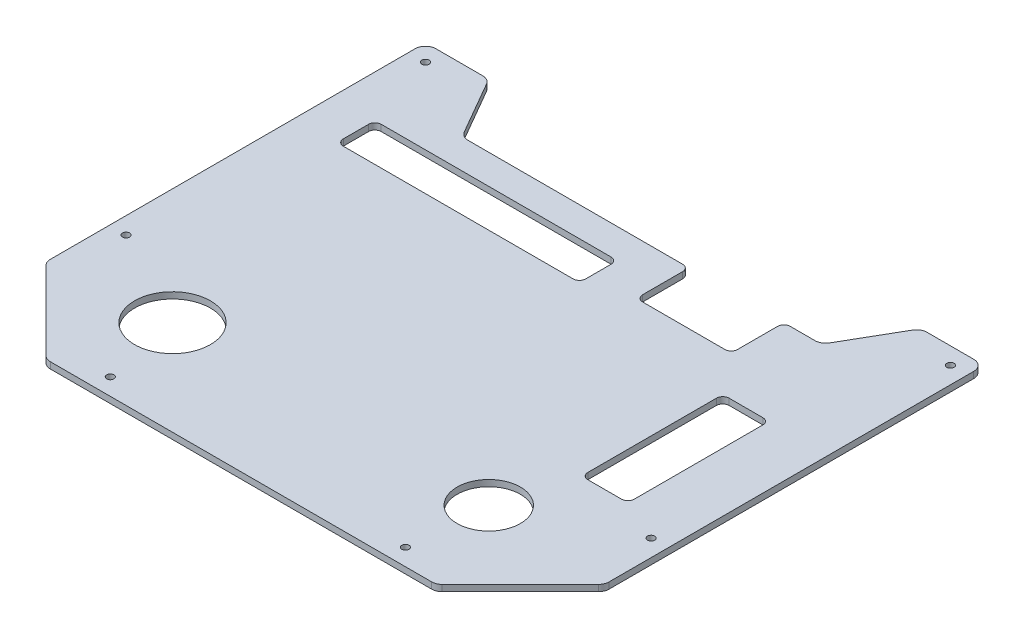
SolidWorks part; units mm, degrees
material "Acier non allié"
ref_plane "Front" through (0, 0, 0) normal (0, 0, 1) x (1, 0, 0)
ref_plane "Top" through (0, 0, 0) normal (0, 1, 0) x (1, 0, 0)
ref_plane "Right" through (0, 0, 0) normal (1, 0, 0) x (0, 0, -1)
sketch "Esquisse1" plane through (0, 0, 0) normal (0, 1, 0) x (1, 0, 0)
  line L0 (0, 0) -> (0, 1919.0564) construction
  line L1 (-92.5, 0) -> (92.5, 0)
  line L2 (92.5, 0) -> (132.5, 40)
  line L3 (132.5, 40) -> (132.5, 220)
  line L4 (132.5, 220) -> (102.5, 220)
  line L5 (102.5, 220) -> (85.1795, 190)
  line L6 (85.1795, 190) -> (-85.1795, 190)
  line L7 (-102.5, 220) -> (-85.1795, 190)
  line L8 (-132.5, 220) -> (-102.5, 220)
  line L9 (-132.5, 40) -> (-132.5, 220)
  line L10 (-92.5, 0) -> (-132.5, 40)
  point P12 (0, 190)
  dimension "D1" = 132.5
  dimension "D2" = 220
  dimension "D3" = 30
  dimension "D4" = 30
  dimension "D5" = 40
  dimension "D6" = 40
  dimension "D7" = 60
extrude "Boss.-Extru.1" add sketch "Esquisse1" along normal blind 3
fillet "Congé1" radius 5 10 edges at (132.5, 1.5, -220) (102.5, 1.5, -220) (85.1795, 1.5, -190) (-85.1795, 1.5, -190) (-102.5, 1.5, -220) (-132.5, 1.5, -220) (-132.5, 1.5, -40) (-92.5, 1.5, 0) (92.5, 1.5, 0) (132.5, 1.5, -40)
sketch "Esquisse2" plane through (0, 0, 0) normal (0, -1, 0) x (1, 0, 0)
  line L0 (0, 0) -> (0, -330.9968) construction
  line L1 (-90.4289, 0) -> (90.4289, 0) construction
  line L2 (-105.3868, -220) -> (-127.5, -220) construction
  line L3 (-132.5, -215) -> (-132.5, -42.0711) construction
  circle A0 centre (-70, -8) radius 1
  circle A1 centre (-124.5, -70) radius 1
  circle A2 centre (-124.5, -212) radius 1
  circle A3 centre (124.5, -212) radius 1
  circle A4 centre (124.5, -70) radius 1
  circle A5 centre (70, -8) radius 1
  dimension "D3" = 2
  dimension "D6" = 2
  dimension "D9" = 2
  dimension "D1" = 70
  dimension "D2" = 8
  dimension "D4" = 124.5
  dimension "D5" = 70
  dimension "D7" = 8
  dimension "D8" = 8
extrude "Enlèv. mat.-Extru.1" cut sketch "Esquisse2" against normal through all
hole_wizard "Dégagement M31" positions "Esquisse3" profile "Esquisse4" hole size "M3" standard "ISO" end condition through all
sketch "Esquisse3" plane through (0, 0, 0) normal (0, -1, 0) x (-1, 0, 0)
  point P0 (-70, 8)
  point P3 (-124.5, 70)
  point P6 (-124.5, 212)
  point P9 (124.5, 212)
  point P12 (124.5, 70)
  point P15 (70, 8)
sketch "Esquisse4" plane through (70, 0, -8) normal (1, 0, 0) x (0, 0, -1)
  line L0 (0, 0) -> (0, 3)
  line L1 (0, 3) -> (1.7, 3)
  line L2 (1.7, 3) -> (1.7, 0)
  line L5 (1.7, 0) -> (0, 0)
  line L11 (0, -6.35) -> (0, 107.95) construction
  dimension "Diamètre du perçage jusqu'au prochain" = 3.4
  dimension "Profondeur du perçage jusqu'au prochain" = 3
sketch "Esquisse5" plane through (0, 0, 0) normal (0, -1, 0) x (1, 0, 0)
  line L6 (82.2927, -190) -> (-82.2927, -190) construction
  line L7 (22.5, -190) -> (67.5, -190)
  line L20 (22.5, -190) -> (22.5, -165)
  line L21 (22.5, -165) -> (67.5, -165)
  line L22 (67.5, -190) -> (67.5, -165)
  line L23 (132.5, -42.0711) -> (132.5, -215) construction
  line L24 (-105.3868, -220) -> (-127.5, -220) construction
  line L25 (-112.5, -176) -> (2.5, -176)
  line L26 (-112.5, -176) -> (-112.5, -158)
  line L27 (-112.5, -158) -> (2.5, -158)
  line L28 (2.5, -176) -> (2.5, -158)
  line L29 (-132.5, -215) -> (-132.5, -42.0711) construction
  line L30 (127.5, -220) -> (105.3868, -220) construction
  line L31 (82.5, -146) -> (104.5, -146)
  line L32 (82.5, -146) -> (82.5, -79)
  line L33 (82.5, -79) -> (104.5, -79)
  line L34 (104.5, -146) -> (104.5, -79)
  line L35 (-90.4289, 0) -> (90.4289, 0) construction
  circle A0 centre (-77.5, -45) radius 18
  circle A1 centre (72.5, -45) radius 15
  dimension "D14" = 36
  dimension "D17" = 30
  dimension "D1" = 65
  dimension "D2" = 110
  dimension "D3" = 25
  dimension "D4" = 62
  dimension "D5" = 135
  dimension "D6" = 18
  dimension "D7" = 115
  dimension "D8" = 50
  dimension "D9" = 74
  dimension "D10" = 67
  dimension "D11" = 22
  dimension "D12" = 55
  dimension "D13" = 45
  dimension "D15" = 60
  dimension "D16" = 45
extrude "Enlèv. mat.-Extru.2" cut sketch "Esquisse5" against normal through all
fillet "Congé2" radius 3 12 edges at (67.5, 1.5, -190) (67.5, 1.5, -165) (22.5, 1.5, -165) (22.5, 1.5, -190) (104.5, 1.5, -146) (82.5, 1.5, -146) (82.5, 1.5, -79) (104.5, 1.5, -79) (2.5, 1.5, -158) (2.5, 1.5, -176) (-112.5, 1.5, -158) (-112.5, 1.5, -176)
equation "\"WIDTH\"= 300mm'Total width of the robot"
equation "\"LENGTH\"= 220mm'Total length of the robot"
equation "\"CUT_DEPTH\"= 45mm'Depth of the cut on the edges of the plate"
equation "\"Plate_th\"= 3mm'Thickness of the plate"
equation "\"D1\"= \"Plate_th\""
